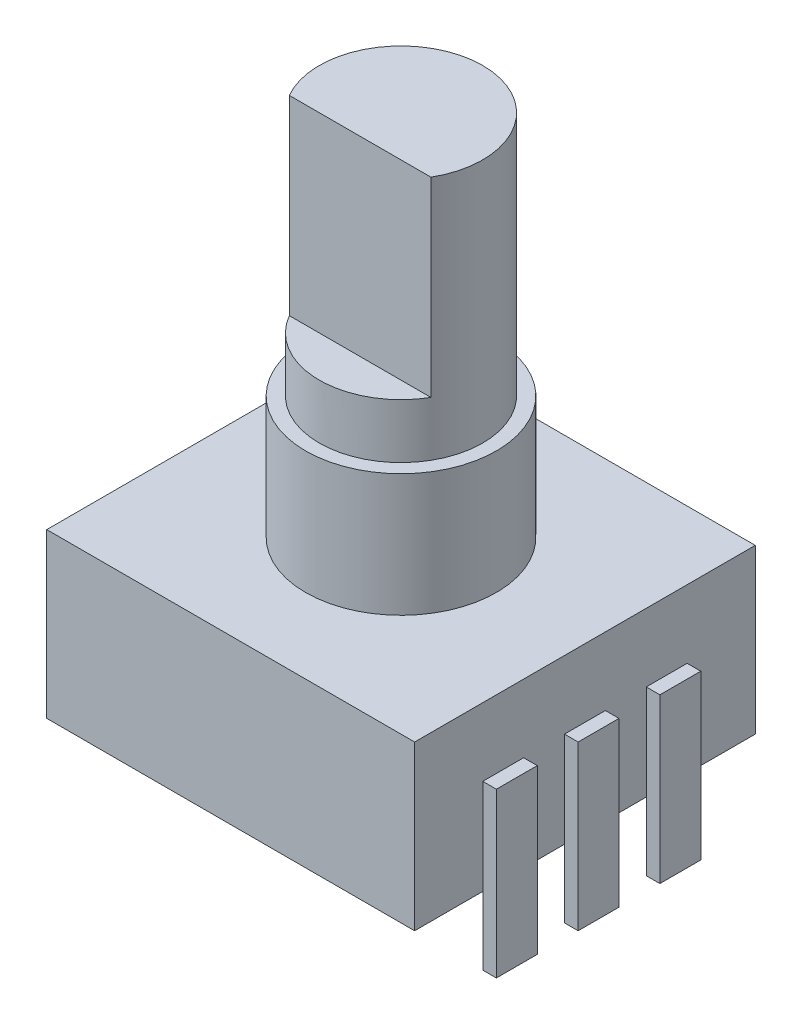
SolidWorks part; units mm, degrees
ref_plane "Front" through (0, 0, 0) normal (0, 0, 1) x (1, 0, 0)
ref_plane "Top" through (0, 0, 0) normal (0, 1, 0) x (1, 0, 0)
ref_plane "Right" through (0, 0, 0) normal (1, 0, 0) x (0, 0, -1)
sketch "Эскиз1" plane through (0, 0, 0) normal (0, 1, 0) x (1, 0, 0)
  line L0 (-2.5981, -1.5) -> (2.5981, -1.5)
  line L1 (-6.75, 6.25) -> (6.75, 6.25)
  line L2 (-6.75, 6.25) -> (-6.75, -6.25)
  line L3 (-6.75, -6.25) -> (6.75, -6.25)
  line L4 (6.75, 6.25) -> (6.75, -6.25)
  line L5 (-6.75, 6.25) -> (6.75, -6.25) construction
  line L6 (-6.75, -6.25) -> (6.75, 6.25) construction
  circle A0 centre (0, 0) radius 3.5
  circle A1 centre (0, 0) radius 3
  point P0 (0, 0)
  dimension "D3" = 7
  dimension "D5" = 6
  dimension "D1" = 13.5
  dimension "D2" = 12.5
  dimension "D4" = 1.5
extrude "Бобышка-Вытянуть1" add sketch "Эскиз1" along normal blind 13.5 contours L0 A1 region at (0, 0, -0.514)
extrude "Бобышка-Вытянуть2" add sketch "Эскиз1<3>" along normal blind 6.5 contours L0 A1 region at (0, 0, 2.1151)
sketch "Эскиз1<3>" plane through (0, 0, 0) normal (0, 1, 0) x (1, 0, 0) same geometry as "Эскиз1"
extrude "Бобышка-Вытянуть3" add sketch "Эскиз1<4>" along normal blind 4.5 contours A0
sketch "Эскиз1<4>" plane through (0, 0, 0) normal (0, 1, 0) x (1, 0, 0) same geometry as "Эскиз1"
extrude "Бобышка-Вытянуть4" add sketch "Эскиз1<5>" against normal blind 6 separate body contours L4 L1 L2 L3 A0 region at (0, 0, -6.066)
sketch "Эскиз1<5>" plane through (0, 0, 0) normal (0, 1, 0) x (1, 0, 0) same geometry as "Эскиз1"
sketch "Эскиз2" plane through (0, 0, 0) normal (0, 1, 0) x (1, 0, 0)
  line L0 (6.75, 6.25) -> (6.75, -6.25) construction
  line L1 (6.75, 3.75) -> (7.25, 3.75)
  line L2 (6.75, 3.75) -> (6.75, 2.25)
  line L3 (6.75, 2.25) -> (7.25, 2.25)
  line L4 (7.25, 3.75) -> (7.25, 2.25)
  line L5 (-6.75, 0) -> (6.75, 0) construction
  line L6 (6.75, 0.75) -> (7.25, 0.75)
  line L7 (6.75, 0.75) -> (6.75, -0.75)
  line L8 (6.75, -0.75) -> (7.25, -0.75)
  line L9 (7.25, 0.75) -> (7.25, -0.75)
  line L10 (6.75, -2.25) -> (7.25, -2.25)
  line L11 (6.75, -2.25) -> (6.75, -3.75)
  line L12 (6.75, -3.75) -> (7.25, -3.75)
  line L13 (7.25, -2.25) -> (7.25, -3.75)
  line L14 (-6.75, 6.25) -> (-6.75, -6.25) construction
  line L15 (-6.75, 6.25) -> (6.75, 6.25) construction
  line L16 (-6.75, 3.5) -> (-7.25, 3.5)
  line L17 (-6.75, 3.5) -> (-6.75, 2)
  line L18 (-6.75, 2) -> (-7.25, 2)
  line L19 (-7.25, 3.5) -> (-7.25, 2)
  line L20 (-6.75, -3.5) -> (-7.25, -3.5)
  line L21 (-6.75, -3.5) -> (-6.75, -2)
  line L22 (-6.75, -2) -> (-7.25, -2)
  line L23 (-7.25, -3.5) -> (-7.25, -2)
  dimension "D1" = 4
  dimension "D2" = 1.5
  dimension "D3" = 2.5
  dimension "D4" = 0.5
extrude "Бобышка-Вытянуть5" add sketch "Эскиз2" against normal blind 6 from offset 2.5 offset against normal yes
